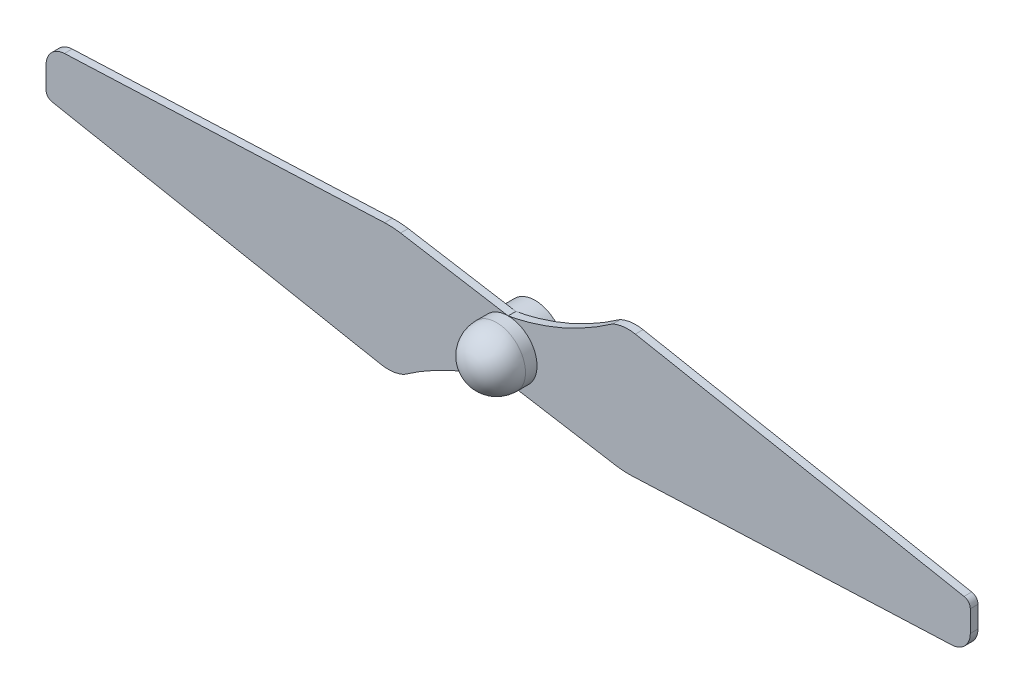
SolidWorks part; units mm, degrees
ref_plane "정면" through (0, 0, 0) normal (0, 0, 1) x (1, 0, 0)
ref_plane "윗면" through (0, 0, 0) normal (0, 1, 0) x (1, 0, 0)
ref_plane "우측면" through (0, 0, 0) normal (1, 0, 0) x (0, 0, -1)
sketch "스케치1" plane through (0, 0, 0) normal (0, 0, 1) x (1, 0, 0)
  circle A0 centre (0, 0) radius 7.5
  dimension "D1" = 15
extrude "보스-돌출1" add sketch "스케치1" along normal blind 10
ref_axis "기준축1" through (0, 0, 10) along (0, 0, -1)
ref_plane "평면2" through (0, 0, 10) normal (0, 0, 1) x (1, 0, 0)
sketch "스케치3" plane through (0, 0, 10) normal (0, 0, 1) x (1, 0, 0)
  line L0 (0, 0) -> (0, -8.1689) construction
ref_plane "평면3" through (0, 0, 0) normal (-1, 0, 0) x (0, -1, 0)
sketch "스케치4" plane through (0, 0, 0) normal (-1, 0, 0) x (0, -1, 0)
  line L0 (-7.5, 10) -> (7.5, 10)
  arc A0 (7.5, 10) -> (-7.5, 10) centre (0, 10) ccw
revolve "회전4" add sketch "스케치4" angle 360 about L0 region at (0, 0, 13.1831)
sketch "스케치5" plane through (0, 0, 0) normal (0, 0, -1) x (-1, 0, 0)
  circle A0 centre (0, 0) radius 2.5
  dimension "D1" = 5
extrude "컷-돌출1" cut sketch "스케치5" against normal blind 14
ref_plane "평면4" through (0, 0, 5) normal (0, 0, -1) x (-1, 0, 0)
sketch "스케치7" plane through (0, 0, 5) normal (0, 0, -1) x (-1, 0, 0)
  line L0 (0, 22.5) -> (0, -22.5) construction
  line L2 (120, -1.6382) -> (120, 3.9142)
  line L6 (33.0266, -19.9213) -> (118.3756, -3.6026)
  line L7 (120, -1.6382) -> (120, 3.9142)
  line L8 (115.2105, 8.9098) -> (32.0782, 12.4124)
  line L9 (27.9483, 12.158) -> (0, 7.5)
  line L10 (27.1726, -19.2748) -> (14.0344, -10.0811) construction
  line L11 (14.0344, -10.0811) -> (0, -7.5) construction
  line L12 (-120, 1.6382) -> (-120, -3.9142)
  line L13 (-33.0266, 19.9213) -> (-118.3756, 3.6026)
  line L14 (-120, 1.6382) -> (-120, -3.9142)
  line L15 (-115.2105, -8.9098) -> (-32.0782, -12.4124)
  line L16 (-27.9483, -12.158) -> (0, -7.5)
  line L17 (0, -22.5) -> (0, 22.5) construction
  line L18 (-27.1726, 19.2748) -> (-14.0344, 10.0811) construction
  line L19 (-14.0344, 10.0811) -> (0, 7.5) construction
  line L20 (0, 0) -> (0, 7.5) construction
  circle A0 centre (0, 0) radius 7.5 construction
  arc A1 (27.1726, -19.2748) -> (33.0266, -19.9213) centre (31.1487, -10.0992) ccw
  arc A2 (32.0782, 12.4124) -> (27.9483, 12.158) centre (31.2363, -7.5698) ccw
  arc A3 (120, 3.9142) -> (115.2105, 8.9098) centre (115, 3.9142) ccw
  arc A4 (118.3756, -3.6026) -> (120, -1.6382) centre (118, -1.6382) ccw
  arc A5 (-27.1726, 19.2748) -> (-33.0266, 19.9213) centre (-31.1487, 10.0992) ccw
  arc A6 (-32.0782, -12.4124) -> (-27.9483, -12.158) centre (-31.2363, 7.5698) ccw
  arc A7 (-120, -3.9142) -> (-115.2105, -8.9098) centre (-115, -3.9142) ccw
  arc A8 (-118.3756, 3.6026) -> (-120, 1.6382) centre (-118, 1.6382) ccw
  spline S0 degree 2 poles (27.1726, -19.2748) (14.0344, -10.0811) (0, -7.5) knots 0 0 0 1 1 1
  spline S1 degree 2 poles (-27.1726, 19.2748) (-14.0344, 10.0811) (0, 7.5) knots 0 0 0 1 1 1
  point P18 (30, -20.5)
  point P21 (30, 12.5)
  point P24 (120, 8.708)
  point P27 (120, -3.292)
  point P37 (-30, 20.5)
  dimension "D8" = 10
  dimension "D9" = 20
  dimension "D10" = 5
  dimension "D11" = 2
  dimension "D2" = 2
  dimension "D3" = 12
  dimension "D4" = 30
  dimension "D5" = 5
  dimension "D6" = 30
  dimension "D7" = 13
  dimension "D12" = 7.5
extrude "보스-돌출2" add sketch "스케치7" against normal blind 2 contours S1 A5 L13 A8 L12 A7 L15 A6 L16 S0 A1 L6 A4 L2 A3 L8 A2 L9 region at (0, 0, 5)
sketch "스케치8" plane through (0, 0, 0) normal (0, 0, -1) x (-1, 0, 0)
  circle A0 centre (0, 0) radius 2.5
extrude "컷-돌출2" cut sketch "스케치8" against normal blind 12
